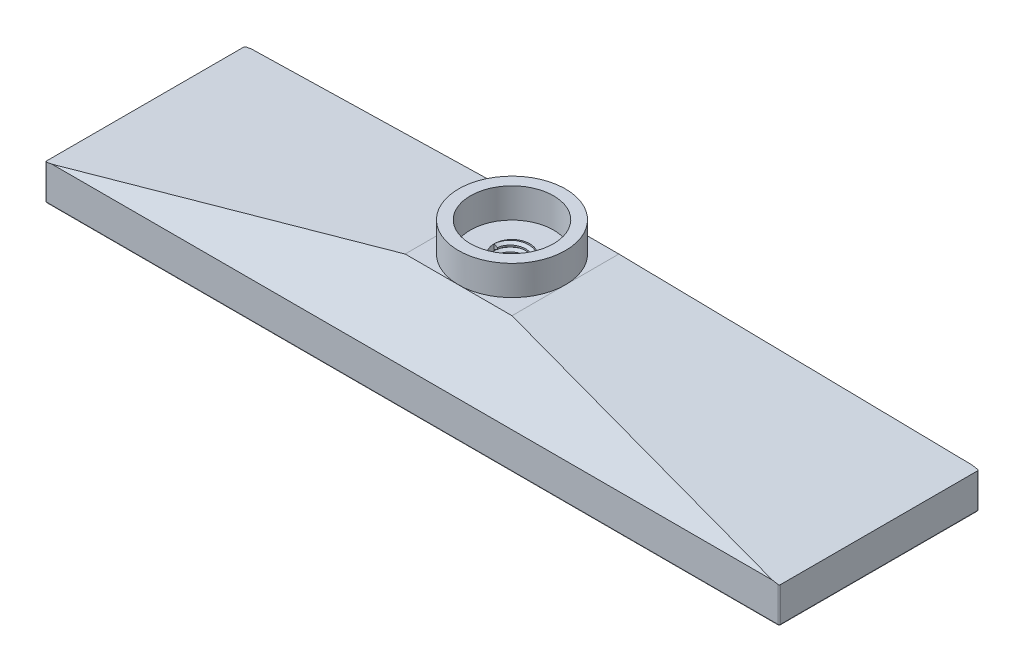
SolidWorks part; units mm, degrees
ref_plane "Front Plane" through (0, 0, 0) normal (0, 0, 1) x (1, 0, 0)
ref_plane "Top Plane" through (0, 0, 0) normal (0, 1, 0) x (1, 0, 0)
ref_plane "Right Plane" through (0, 0, 0) normal (1, 0, 0) x (0, 0, -1)
sketch "Sketch1" plane through (0, 0, 0) normal (0, 1, 0) x (1, 0, 0)
  line L1 (60, 15) -> (-60, 15)
  line L2 (60, 15) -> (60, -15)
  line L3 (60, -15) -> (-60, -15)
  line L4 (-60, 15) -> (-60, -15)
  line L5 (60, 15) -> (-60, -15) construction
  line L6 (60, -15) -> (-60, 15) construction
  point P0 (0, 0)
  dimension "D1" = 120
  dimension "D2" = 30
extrude "Boss-Extrude1" add sketch "Sketch1" along normal blind 15
sketch "Sketch2" plane through (0, 0, 0) normal (0, 1, 0) x (1, 0, 0)
  line L4 (-60, 15) -> (-60, -15)
  line L5 (60, 15) -> (-60, 15)
  line L6 (60, -15) -> (60, 15)
  line L7 (-60, -15) -> (60, -15)
  line L8 (-60, 15) -> (-60, -15)
  line L9 (60, 15) -> (-60, 15)
  line L10 (60, -15) -> (60, 15)
  line L11 (-60, -15) -> (60, -15)
  dimension "D1" = 0
extrude "Extrude-Thin1" add sketch "Sketch2" along normal blind 15 thin thin type one direction wall 2
ref_plane "Plane1" through (0, 10, 0) normal (0, 1, 0) x (1, 0, 0)
sketch "Sketch7" plane through (0, 10, 0) normal (0, 1, 0) x (1, 0, 0)
  line L1 (-1.5, 1.5) -> (1.5, 1.5)
  line L2 (-1.5, 1.5) -> (-1.5, -1.5)
  line L3 (-1.5, -1.5) -> (1.5, -1.5)
  line L4 (1.5, 1.5) -> (1.5, -1.5)
  line L5 (-1.5, 1.5) -> (1.5, -1.5) construction
  line L6 (-1.5, -1.5) -> (1.5, 1.5) construction
  point P0 (0, 0)
  dimension "D2" = 3
loft "Cut-Loft3" cut profiles "Sketch1<4>", "Sketch7" connector at (-60, 0, 15) connector at (-1.5, 10, 1.5)
sketch "Sketch1<4>" plane through (0, 0, 0) normal (0, 1, 0) x (1, 0, 0) same geometry as "Sketch1"
sketch "Sketch10" plane through (0, 15, 0) normal (0, 1, 0) x (1, 0, 0)
  line L0 (-62, 17) -> (-62, -17) construction
  line L1 (8.6603, -5) -> (8.6603, 5)
  line L2 (8.6603, 5) -> (0, 10)
  line L3 (0, 10) -> (-8.6603, 5)
  line L4 (-8.6603, 5) -> (-8.6603, -5)
  line L5 (-8.6603, -5) -> (0, -10)
  line L6 (0, -10) -> (8.6603, -5)
  circle A0 centre (0, 0) radius 8.6603 construction
  dimension "D1" = 10
sketch "Sketch12" plane through (0, 10, 0) normal (0, 1, 0) x (1, 0, 0)
  circle A0 centre (0, 0) radius 3
  dimension "D1" = 6
extrude "Cut-Extrude4" cut sketch "Sketch12" along normal blind 15 and the other way blind 2
sketch "Sketch13" plane through (0, 15, 0) normal (0, 1, 0) x (1, 0, 0)
  circle A0 centre (0, 0) radius 7
  dimension "D1" = 14
extrude "Extrude-Thin2" add sketch "Sketch13" along normal blind 5 thin thin type one direction wall 2
thread "Thread2" pitch 1 method extrude profile "Thread Profile3" start angle 0, offset 0, length 5, pitch 1, diameter 6
ref_plane "Plane4" through (-3, 15, 0) normal (0, 0, 1) x (-1, 0, 0)
sketch "Thread Profile3" plane through (-3, 15, 0) normal (0, 0, 1) x (-1, 0, 0)
  line L0 (0, 0) -> (0, 1) construction
  line L11 (0, 0) -> (0, 0.875)
  line L12 (0, 0.875) -> (-0.5413, 0.5625)
  line L13 (-0.5413, 0.5625) -> (-0.5413, 0.3125)
  line L15 (-0.5413, 0.3125) -> (0, 0)
  line L17 (-0.5413, 0.4375) -> (0, 0.4375) construction
  point P2 (0, 0)
  dimension "Pitch" = 1
  dimension "Profile_Angle" = 60
  dimension "Profile_Land" = 0.25
  dimension "Profile_Height" = 0.5413
sketch "Skizze1" plane through (0, 0, -17) normal (0, 0, -1) x (-1, 0, 0)
  line L0 (-62, 5.9402) -> (-9, 15)
  line L1 (-62, 15) -> (-62, 0) construction
  line L2 (-62, 15) -> (62, 15) construction
  line L3 (-9, 15) -> (-62, 15)
  line L4 (-62, 15) -> (-62, 5.9402)
  line L10 (0, 20) -> (0, -27.2795) construction
  line L11 (9, 20) -> (-9, 20) construction
  line L13 (62, 15) -> (62, 5.9402)
  line L14 (9, 15) -> (62, 15)
  line L15 (62, 5.9402) -> (9, 15)
  line L16 (-60, 0) -> (-2.4573, 9.8364) construction
extrude "Schnitt-Linear austragen1" cut sketch "Skizze1" against normal through all
sketch "Skizze2" plane through (-62, 0, 0) normal (-1, 0, 0) x (0, 0, 1)
  line L0 (-17, 5.9402) -> (-9, 15)
  line L1 (-9, 15) -> (-17, 15)
  line L2 (-17, 15) -> (-17, 5.9402)
  line L3 (9, 15) -> (17, 5.9402)
  line L4 (17, 5.9402) -> (17, 15)
  line L5 (17, 15) -> (9, 15)
extrude "Schnitt-Linear austragen2" cut sketch "Skizze2" against normal through all
sketch "Skizze4" plane through (0, 0, 0) normal (0, -1, 0) x (-1, 0, 0)
  line L0 (62, -17) -> (-62, -17) construction
  line L1 (64.8639, 19.768) -> (-64.8639, 19.768)
  line L2 (64.8639, 19.768) -> (64.8639, -19.768)
  line L3 (64.8639, -19.768) -> (-64.8639, -19.768)
  line L4 (-64.8639, 19.768) -> (-64.8639, -19.768)
  line L5 (64.8639, 19.768) -> (-64.8639, -19.768) construction
  line L6 (64.8639, -19.768) -> (-64.8639, 19.768) construction
  line L7 (61.8, 16.8) -> (-61.8, 16.8)
  line L8 (61.8, 16.8) -> (61.8, -16.8)
  line L9 (61.8, -16.8) -> (-61.8, -16.8)
  line L10 (-61.8, 16.8) -> (-61.8, -16.8)
  line L11 (61.8, 16.8) -> (-61.8, -16.8) construction
  line L12 (61.8, -16.8) -> (-61.8, 16.8) construction
  line L13 (62, 17) -> (62, -17) construction
  point P0 (0, 0)
  point P5 (0, 0)
  dimension "D1" = 0.2
  dimension "D2" = 0.2
extrude "Schnitt-Linear austragen3" cut sketch "Skizze4" against normal through all
fillet "Verrundung1" radius 0.2 8 edges at (0, 0, -16.8) (61.8, 0, 0) (0, 0, 16.8) (-61.8, 0, 0) (-61.8, 2.9872, -16.8) (61.8, 2.9872, -16.8) (61.8, 2.9872, 16.8) (-61.8, 2.9872, 16.8)
